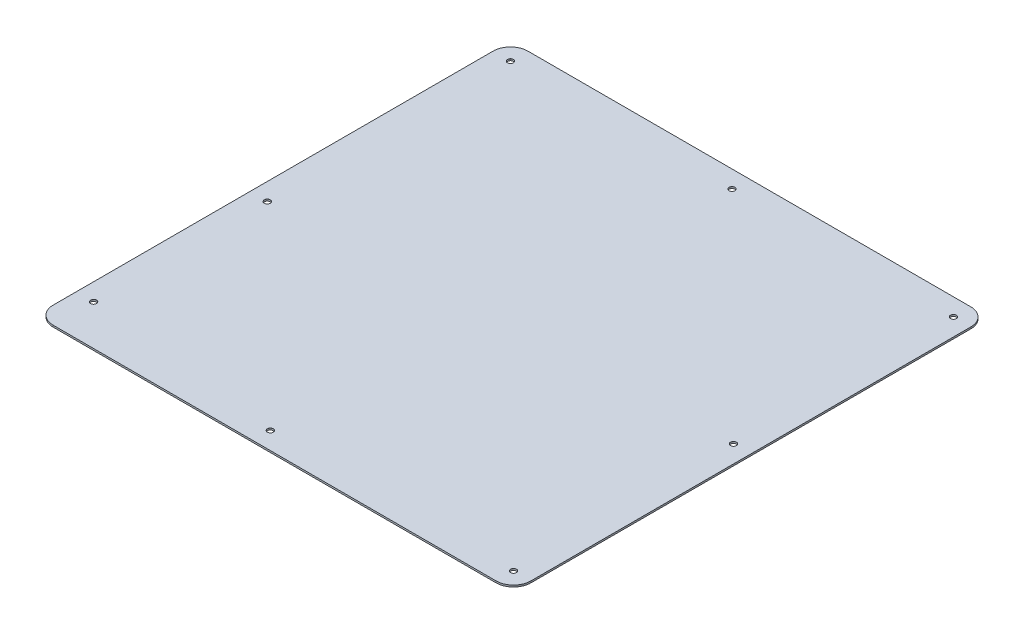
SolidWorks part; units mm, degrees
ref_plane "Front Plane" through (0, 0, 0) normal (0, 0, 1) x (1, 0, 0)
ref_plane "Top Plane" through (0, 0, 0) normal (0, 1, 0) x (1, 0, 0)
ref_plane "Right Plane" through (0, 0, 0) normal (1, 0, 0) x (0, 0, -1)
sketch "Sketch1" plane through (0, 0, 0) normal (0, 1, 0) x (1, 0, 0)
  line L1 (-137.5, 136.635) -> (137.5, 136.635)
  line L2 (-137.5, 136.635) -> (-137.5, -136.635)
  line L3 (-137.5, -136.635) -> (137.5, -136.635)
  line L4 (137.5, 136.635) -> (137.5, -136.635)
  line L5 (-137.5, 136.635) -> (137.5, -136.635) construction
  line L6 (-137.5, -136.635) -> (137.5, 136.635) construction
  point P0 (0, 0)
  dimension "D1" = 275
  dimension "D2" = 273.27
extrude "Boss-Extrude1" add sketch "Sketch1" along normal blind 1
fillet "Fillet1" radius 10 4 edges at (-137.5, 0.5, 136.635) (137.5, 0.5, 136.635) (137.5, 0.5, -136.635) (-137.5, 0.5, -136.635)
hole_wizard "M3 Clearance Hole2" positions "Sketch6" profile "Sketch7" hole size "M3" standard "ANSI Metric" end condition through all
sketch "Sketch6" plane through (0, 1, 0) normal (0, 1, 0) x (1, 0, 0)
  point P0 (0, 126.635)
  point P3 (127.5, 126.635)
  point P6 (-127.5, 126.6311)
  point P9 (-127.5, -13.3689)
  point P12 (-127.5, -113.3689)
  point P15 (-12.5, -126.6328)
  point P18 (127.5, -126.6328)
  point P21 (127.5, 0)
sketch "Sketch7" plane through (0, 1, -126.635) normal (1, 0, 0) x (0, 0, 1)
  line L0 (0, 0) -> (0, 1)
  line L1 (0, 1) -> (1.7, 1)
  line L2 (1.7, 1) -> (1.7, 0.025)
  line L3 (1.7, 0.025) -> (1.725, 0)
  line L5 (1.725, 0) -> (0, 0)
  line L6 (-1.7, 0.025) -> (-1.725, 0) construction
  line L11 (0, -6.35) -> (0, 107.95) construction
  dimension "Thru Hole Dia." = 3.4
  dimension "Thru Hole Depth" = 1
  dimension "Near C'Sink Dia." = 3.45
  dimension "Near C'Sink Angle" = 90
